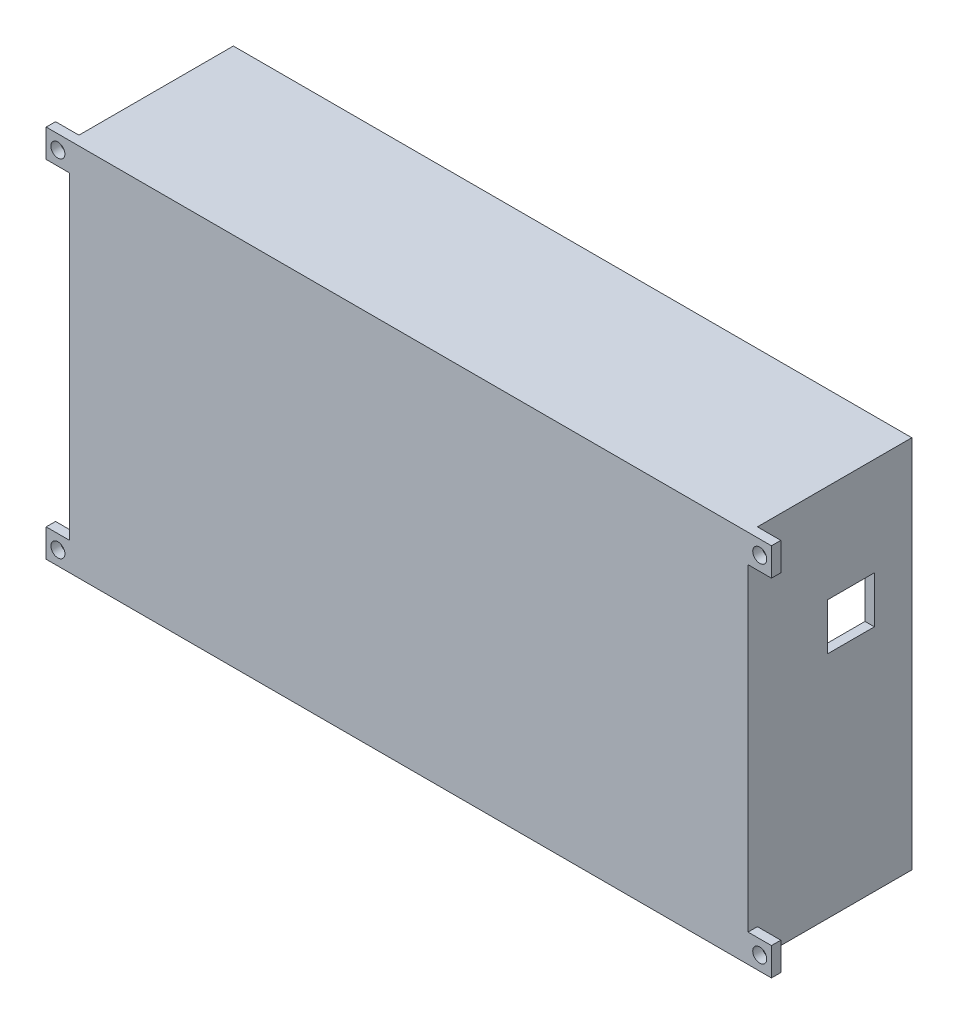
SolidWorks part; units mm, degrees
ref_plane "Спереди" through (0, 0, 0) normal (0, 0, 1) x (1, 0, 0)
ref_plane "Сверху" through (0, 0, 0) normal (0, 1, 0) x (1, 0, 0)
ref_plane "Справа" through (0, 0, 0) normal (1, 0, 0) x (0, 0, -1)
sketch "Эскиз1" plane through (0, 0, 0) normal (0, 0, 1) x (1, 0, 0)
  line L1 (0, 0) -> (145, 0)
  line L2 (0, 0) -> (0, 80)
  line L3 (0, 80) -> (145, 80)
  line L4 (145, 0) -> (145, 80)
  dimension "D1" = 145
  dimension "D2" = 80
extrude "Бобышка-Вытянуть1" add sketch "Эскиз1" along normal blind 35
sketch "Эскиз2" plane through (0, 0, 0) normal (0, 0, -1) x (-1, 0, 0)
  line L0 (-145, 0) -> (-145, 80) construction
  line L1 (-143, 2) -> (-2, 2)
  line L2 (-143, 2) -> (-143, 78)
  line L3 (-143, 78) -> (-2, 78)
  line L4 (-2, 2) -> (-2, 78)
  line L5 (0, 0) -> (-145, 0) construction
  line L6 (0, 80) -> (0, 0) construction
  line L7 (-145, 80) -> (0, 80) construction
  dimension "D1" = 2
  dimension "D2" = 2
  dimension "D3" = 2
  dimension "D4" = 2
extrude "Вырез-Вытянуть1" cut sketch "Эскиз2" against normal blind 33
sketch "Эскиз3" plane through (0, 0, 33) normal (0, 0, -1) x (-1, 0, 0)
  line L0 (-143, 40) -> (3.9467, 40) construction
  line L1 (-143, 78) -> (-143, 2) construction
  line L3 (-143, 78) -> (-143, 2) construction
  circle A0 centre (-109.79, 62.86) radius 3.5
  circle A1 centre (-109.79, 17.14) radius 3.5
  circle A2 centre (-34.79, 64.13) radius 3.5
  circle A3 centre (-34.79, 15.87) radius 3.5
  point P8 (-202.8123, 30.4132)
  point P9 (0, 0)
  point P14 (0, 0)
  point P15 (0, 0)
  dimension "D1" = 7
  dimension "D2" = 7
  dimension "D4" = 7
  dimension "D5" = 7
  dimension "D3" = 45.72
  dimension "D6" = 48.26
  dimension "D7" = 75
  dimension "D8" = 33.21
extrude "Бобышка-Вытянуть2" add sketch "Эскиз3" along normal blind 15
sketch "Эскиз4" plane through (0, 0, 18) normal (0, 0, -1) x (-1, 0, 0)
  circle A0 centre (-109.79, 62.86) radius 1.5
  circle A1 centre (-34.79, 64.13) radius 1.5
  circle A2 centre (-34.79, 15.87) radius 1.5
  circle A3 centre (-109.79, 17.14) radius 1.5
  point P5 (-34.79, 59.13)
  point P9 (-34.79, 10.87)
  point P13 (-109.79, 12.14)
  point P15 (0, 0)
  dimension "D1" = 3
  dimension "D2" = 3
  dimension "D3" = 3
  dimension "D4" = 3
extrude "Вырез-Вытянуть2" cut sketch "Эскиз4" against normal blind 15
sketch "Эскиз5" plane through (0, 0, 0) normal (-1, 0, 0) x (0, 0, 1)
  line L1 (8, 31) -> (18, 31)
  line L2 (8, 31) -> (8, 21)
  line L3 (8, 21) -> (18, 21)
  line L4 (18, 31) -> (18, 21)
  line L5 (35, 80) -> (35, 0) construction
  line L6 (35, 0) -> (0, 0) construction
  line L9 (35, 80) -> (0, 80) construction
  line L10 (6, 62) -> (22, 62)
  line L11 (6, 62) -> (6, 41)
  line L12 (6, 41) -> (22, 41)
  line L13 (22, 62) -> (22, 41)
  point P4 (18, 26)
  dimension "D1" = 10
  dimension "D2" = 10
  dimension "D3" = 21
  dimension "D4" = 17
  dimension "D5" = 21
  dimension "D6" = 16
  dimension "D7" = 18
  dimension "D8" = 13
extrude "Вырез-Вытянуть3" cut sketch "Эскиз5" against normal blind 15
sketch "Эскиз6" plane through (143, 0, 0) normal (-1, 0, 0) x (0, 0, 1)
  line L0 (35, 80) -> (0, 80) construction
  line L1 (8, 59) -> (18, 59)
  line L2 (8, 59) -> (8, 49)
  line L3 (8, 49) -> (18, 49)
  line L4 (18, 59) -> (18, 49)
  line L6 (35, 0) -> (35, 80) construction
  dimension "D1" = 10
  dimension "D2" = 10
  dimension "D3" = 21
  dimension "D4" = 17
extrude "Вырез-Вытянуть4" cut sketch "Эскиз6" against normal blind 15
sketch "Эскиз9" plane through (0, 0, 33) normal (0, 0, -1) x (-1, 0, 0)
  line L1 (-2, 78) -> (-143, 78) construction
  line L3 (-2, 2) -> (-2, 78) construction
  circle A0 centre (-4, 76) radius 3.5
  point P2 (-12.2933, 76)
  point P6 (0, 0)
  point P8 (-0.4066, 75.4728)
  dimension "D1" = 7
  dimension "D2" = 2
  dimension "D3" = 2
extrude "Бобышка-Вытянуть3" add sketch "Эскиз9" along normal blind 33
sketch "Эскиз10" plane through (0, 0, 0) normal (0, 0, -1) x (-1, 0, 0)
  circle A0 centre (-4, 76) radius 1.5
  arc A1 (-6.8723, 78) -> (-2, 73.1277) centre (-4, 76) ccw construction
  point P2 (-3.9594, 75.8316)
  point P3 (0, 0)
  point P4 (-3.9298, 75.7614)
  dimension "D1" = 3
  dimension "D2" = 0
extrude "Вырез-Вытянуть5" cut sketch "Эскиз10" against normal blind 33
pattern_linear "Линейный массив2" count 2 spacing 72 along (0, -1, 0) count 2 spacing 137 along (1, 0, 0) of "Вырез-Вытянуть5", "Бобышка-Вытянуть3"
sketch "Эскиз12" plane through (145, 0, 0) normal (1, 0, 0) x (0, 0, -1)
  line L0 (-35, 0) -> (-35, 80) construction
  line L1 (-35, 74) -> (-33, 74)
  line L2 (-35, 74) -> (-35, 80)
  line L3 (-35, 80) -> (-33, 80)
  line L4 (-33, 74) -> (-33, 80)
  line L5 (-35, 80) -> (0, 80) construction
  line L6 (-35, 0) -> (0, 0) construction
  line L7 (-35, 6) -> (-33, 6)
  line L8 (-35, 6) -> (-35, 0)
  line L9 (-35, 0) -> (-33, 0)
  line L10 (-33, 6) -> (-33, 0)
  dimension "D1" = 6
  dimension "D2" = 2
  dimension "D3" = 6
  dimension "D4" = 2
extrude "Бобышка-Вытянуть4" add sketch "Эскиз12" along normal blind 5
sketch "Эскиз13" plane through (0, 0, 33) normal (0, 0, -1) x (-1, 0, 0)
  line L0 (-150, 74) -> (-145, 74) construction
  line L1 (-150, 74) -> (-150, 80) construction
  circle A0 centre (-147.5, 77) radius 1.5
  dimension "D1" = 3
  dimension "D2" = 3
  dimension "D3" = 2.5
extrude "Вырез-Вытянуть6" cut sketch "Эскиз13" against normal blind 5
pattern_linear "Линейный массив3" count 2 spacing 74 along (0, -1, 0) of "Вырез-Вытянуть6"
pattern_linear "Линейный массив4" count 2 spacing 150 along (-1, 0, 0) of "Линейный массив3", "Бобышка-Вытянуть4"
